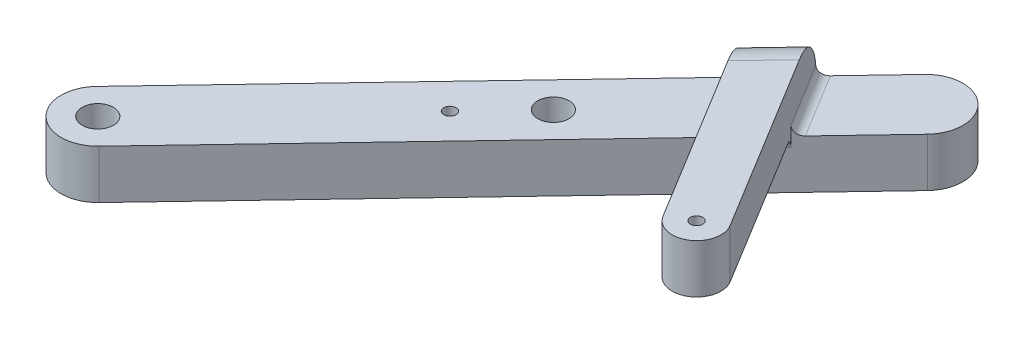
SolidWorks part; units mm, degrees
ref_plane "Front Plane" through (0, 0, 0) normal (0, 0, 1) x (1, 0, 0)
ref_plane "Top Plane" through (0, 0, 0) normal (0, 1, 0) x (1, 0, 0)
ref_plane "Right Plane" through (0, 0, 0) normal (1, 0, 0) x (0, 0, -1)
sketch "Sketch1" plane through (0, 0, 0) normal (0, 1, 0) x (1, 0, 0)
  line L0 (-3.7142, -4.9084) -> (-3.7142, 30.0916) construction
  line L1 (-3.7142, -4.9084) -> (22.7361, 31.4974) construction
  line L2 (-3.7142, 30.0916) -> (21.0919, 32.637) construction
  line L3 (36.805, -32.8652) -> (16.8084, -33.2319) construction
  line L9 (36.805, -32.8652) -> (16.8084, -33.2319)
  line L10 (-9.1489, 0.2602) -> (73.5491, 87.2145)
  line L11 (1.7204, -10.077) -> (84.4184, 76.8772)
  line L12 (-3.7142, -4.9084) -> (58.8778, 60.9051) construction
  line L13 (16.8084, -33.2319) -> (16.9917, -43.2302) construction
  line L14 (16.8084, -33.2319) -> (16.9917, -43.2302)
  line L16 (62.6911, 75.7976) -> (90.3879, 30.489)
  line L17 (55.5565, 68.2958) -> (81.8558, 25.2733)
  circle A0 centre (-3.7142, -4.9084) radius 45 construction
  circle A1 centre (-3.7142, -4.9084) radius 35 construction
  circle A4 centre (-3.7142, -4.9084) radius 3.2
  arc A5 (1.7204, -10.077) -> (-9.1489, 0.2602) centre (-3.7142, -4.9084) cw
  arc A6 (73.5491, 87.2145) -> (84.4184, 76.8772) centre (78.9838, 82.0459) cw
  arc A8 (90.3879, 30.489) -> (81.8558, 25.2733) centre (86.1218, 27.8811) cw
  circle A9 centre (41.7697, 42.9164) radius 3.2
  circle A10 centre (86.1218, 27.8811) radius 1.25
  circle A11 centre (31.4324, 32.0472) radius 1.25
  point P12 (30.7485, 31.4974)
  dimension "D1" = 90
  dimension "D2" = 70
  dimension "D13" = 6.4
  dimension "D14" = 7.5
  dimension "D17" = 7.5
  dimension "D10" = 2.5
  dimension "D24" = 2.5
  dimension "D5" = 6.4
  dimension "D6" = 66
  dimension "D3" = 36
  dimension "D4" = 2
  dimension "D7" = 50
  dimension "D8" = 25
  dimension "D9" = 75
  dimension "D11" = 15
  dimension "D18" = 120
  dimension "D20" = 10
extrude "Boss-Extrude1" add sketch "Sketch1" against normal blind 10 contours A5 L11 L10 A4 | L10 | L10 | L11 L17 L10 L16 | A6 L10 L17 L11 region at (26.1696, 0, -26.5917) region at (63.1735, 0, -65.4219) region at (75.0671, 0, -77.6194)
extrude "Boss-Extrude2" add sketch "Sketch1<7>" along normal blind 10 contours A8 L16 L10 L17 A10 | L11 L17 L10 L16 region at (63.1735, 0, -65.4219) region at (77.6446, 0, -41.8567)
sketch "Sketch1<7>" plane through (0, 0, 0) normal (0, 1, 0) x (1, 0, 0) same geometry as "Sketch1"
fillet "Fillet1" radius 10 1 edges at (59.1238, 10, -72.0467)
fillet "Fillet2" radius 2 2 edges at (59.6062, 0, -61.671) (66.7408, 0, -69.1728)
fillet "Fillet3" radius 2 1 edges at (67.2232, 0, -58.797)
